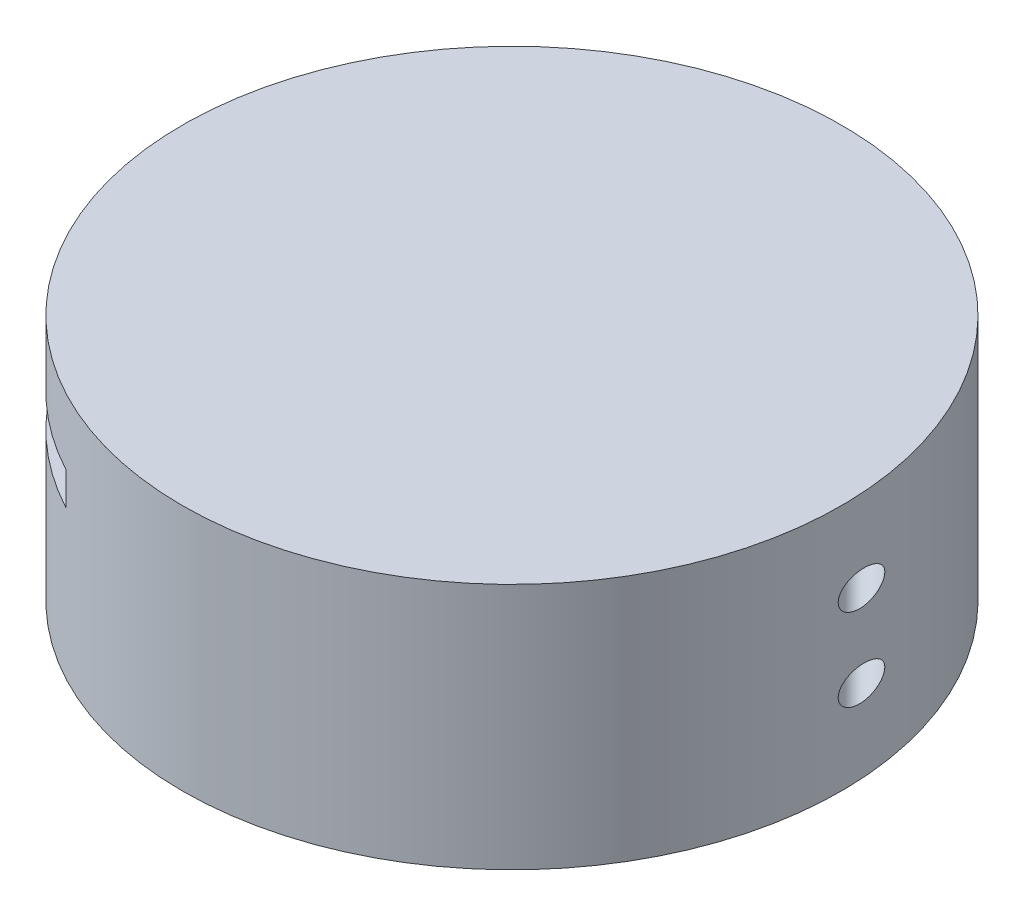
SolidWorks part; units mm, degrees
ref_plane "Front Plane" through (0, 0, 0) normal (0, 0, 1) x (1, 0, 0)
ref_plane "Top Plane" through (0, 0, 0) normal (0, 1, 0) x (1, 0, 0)
ref_plane "Right Plane" through (0, 0, 0) normal (1, 0, 0) x (0, 0, -1)
sketch "Sketch1" plane through (0, 0, 0) normal (0, 1, 0) x (1, 0, 0)
  circle A0 centre (0, 0) radius 20
  dimension "D1" = 40
extrude "Boss-Extrude1" add sketch "Sketch1" along normal blind 15
sketch "Sketch2" plane through (0, 0, 0) normal (0, -1, 0) x (1, 0, 0)
  line L0 (0, 4.0857) -> (0, -4.0857) construction
  line L1 (2.15, 4.0857) -> (2.15, -4.0857)
  line L2 (-2.15, 4.0857) -> (-2.15, -4.0857)
  circle A0 centre (0, 4.0857) radius 3.35
  arc A1 (2.15, 4.0857) -> (-2.15, 4.0857) centre (0, 4.0857) ccw
  arc A2 (-2.15, -4.0857) -> (2.15, -4.0857) centre (0, -4.0857) ccw
  circle A3 centre (0, 0) radius 20 construction
  point P2 (0, 0)
  dimension "D1" = 2.15
  dimension "D2" = 6.7
extrude "Cut-Extrude1" cut sketch "Sketch2" against normal blind 6 contours L2 A2 L1 A0 | L1 A1 L2 A0 | A0 region at (0, 0, 3.397) region at (0, 0, -2.4091)
sketch "Sketch3" plane through (0, 6, 0) normal (0, -1, 0) x (1, 0, 0)
  line L0 (0, -4.0857) -> (0, 4.0857) construction
  line L1 (-3.35, -4.0857) -> (-3.35, 4.0857)
  line L2 (3.35, -4.0857) -> (3.35, 4.0857)
  arc A0 (-3.35, -4.0857) -> (3.35, -4.0857) centre (0, -4.0857) ccw
  arc A1 (3.35, 4.0857) -> (-3.35, 4.0857) centre (0, 4.0857) ccw
  arc A3 (-2.15, -4.0857) -> (2.15, -4.0857) centre (0, -4.0857) ccw construction
  point P3 (0, 0)
  dimension "D1" = 3.35
extrude "Cut-Extrude2" cut sketch "Sketch3" along normal blind 4
ref_plane "Plane1" through (0, 10, 0) normal (0, 1, 0) x (1, 0, 0)
ref_plane "Plane2" through (0, 5, 0) normal (0, -1, 0) x (-1, 0, 0)
sketch "Sketch5" plane through (0, 5, 0) normal (0, -1, 0) x (-1, 0, 0)
  line L0 (-10.6066, 10.6066) -> (-32.7133, -11.5001)
  line L1 (10.6066, 10.6066) -> (41.577, -20.3638)
  line L2 (0, 0) -> (-10.6066, 10.6066) construction
  line L3 (0, 0) -> (10.4461, 0) construction
  line L4 (0, 0) -> (10.6066, 10.6066) construction
  arc A0 (10.6066, 10.6066) -> (-10.6066, 10.6066) centre (0, 0) ccw
  dimension "D1" = 30
  dimension "D2" = 135
  dimension "D3" = 45
sketch "Sketch6" plane through (0, 10, 0) normal (0, 1, 0) x (1, 0, 0)
  line L0 (10.6066, 10.6066) -> (32.7133, -11.5001)
  line L1 (-15, -54.7613) -> (-15, 0)
  line L2 (0, 0) -> (-10.6066, 10.6066) construction
  arc A0 (10.6066, 10.6066) -> (-15, 0) centre (0, 0) ccw
  point P11 (-15, 0)
  dimension "D1" = 45
sweep "Cut-Sweep1" cut path "Sketch6" circular profile diameter 2 parameters "D3"=2
sweep "Cut-Sweep2" cut path "Sketch5" circular profile diameter 2 parameters "D3"=2
sketch "Sketch19" plane through (0, 10, 0) normal (0, 1, 0) x (1, 0, 0)
  line L0 (-14.9497, 5.8707) -> (-14, 0)
  line L1 (-16, 0) -> (-14, 0) construction
  line L2 (-14, 0) -> (-8.6653, -20.6605)
  line L3 (-8.6653, -20.6605) -> (-22.202, -20.6605)
  line L4 (-22.202, -20.6605) -> (-14.9497, 5.8707)
  point P5 (-16.6232, 0)
  point P8 (-15.9849, 0)
  point P9 (0, 0)
  point P10 (-14.9497, 5.8707)
extrude "Cut-Extrude3" cut sketch "Sketch19" against normal blind 1 and the other way blind 1
